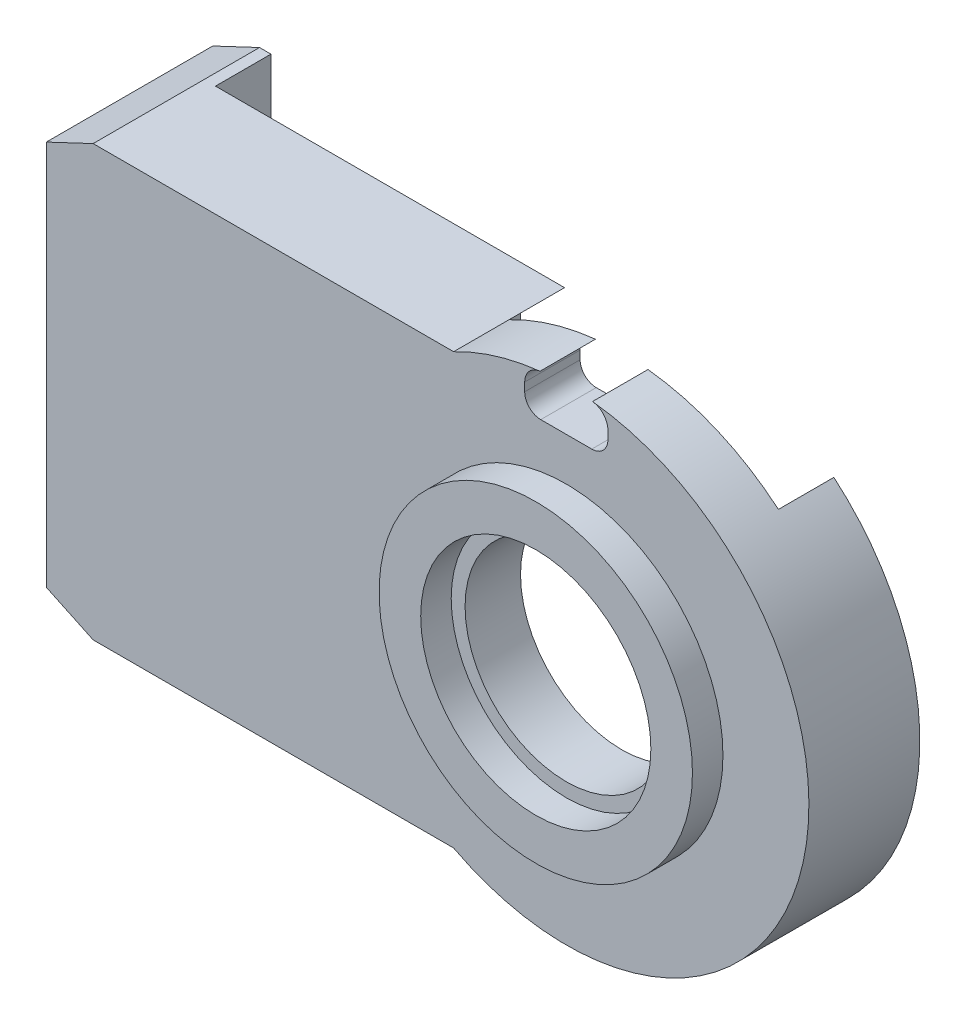
SolidWorks part; units mm, degrees
ref_plane "Спереди" through (0, 0, 0) normal (0, 0, 1) x (1, 0, 0)
ref_plane "Сверху" through (0, 0, 0) normal (0, 1, 0) x (1, 0, 0)
ref_plane "Справа" through (0, 0, 0) normal (1, 0, 0) x (0, 0, -1)
sketch "Эскиз основы" plane through (0, 0, 0) normal (0, 0, 1) x (1, 0, 0)
  line L0 (5.65, 6.6813) -> (5.65, -6.6813)
  line L1 (-5.65, 6.6813) -> (-5.65, -6.6813)
  line L2 (-17.062, 7.75) -> (-18.75, 6.9532)
  line L3 (-17.062, 7.75) -> (-4.062, 7.75)
  line L4 (-17.062, -7.75) -> (-4.062, -7.75)
  line L5 (-4.062, 7.75) -> (-4.062, -7.75)
  line L6 (-17.062, -7.75) -> (-18.75, -6.9532)
  line L11 (-18.75, 6.9532) -> (-18.75, -6.9532)
  line L12 (-16.65, 7.75) -> (-16.65, -7.75)
  arc A0 (-5.65, -6.6813) -> (5.65, -6.6813) centre (0, 0) ccw
  arc A1 (-5.65, -6.6813) -> (5.65, -6.6813) centre (0, 0) ccw
  arc A2 (5.65, 6.6813) -> (-5.65, 6.6813) centre (0, 0) ccw
  circle A3 centre (0, 0) radius 8.75
  circle A10 centre (0, 0) radius 3.65
  point P6 (0, 0)
  point P7 (-4.062, 0)
  point P8 (-18.75, 0)
  point P9 (0, 0)
  point P10 (5.65, 0)
  point P15 (0, 8.75)
  dimension "D1" = 8.75
  dimension "D3" = 17.5
  dimension "D8" = 18.75
  dimension "D11" = 7.3
  dimension "D2" = 11.3
  dimension "D4" = 15.5
  dimension "D5" = 13
  dimension "D6" = 6.9532
  dimension "D9" = 11
extrude "Заготовка" add sketch "Эскиз основы" along normal blind 4 contours L6 L4 A0 A3 A2 L3 L2 | L1 A3 | L5 A2 L1 A0 | L0 A2 L5 A0 | L0 A3 | L2 L11 L6 L4 L5 L3 region at (6.911, 0, 0) region at (5.4499, 0, 0) region at (-11.9356, 0, 0) region at (-4.8366, 0, 0) region at (-6.911, 0, 0)
extrude "Вырез под резистор" cut sketch "Эскиз1<3>" along normal blind 2 contours L0 A2 L5 A0 | L5 A2 L1 A0 region at (5.4499, 0, 0) region at (-4.8366, 0, 0)
sketch "Эскиз1<3>" plane through (0, 0, 0) normal (0, 0, 1) x (1, 0, 0) same geometry as "Эскиз основы"
sketch "Эскиз выемки" plane through (0, 0, 2) normal (0, 0, -1) x (-1, 0, 0)
  line L3 (-3.65, 0) -> (3.65, 0) construction
  line L4 (-1.5, 7.78) -> (-1.5, 8.0822)
  line L5 (1.5, 7.78) -> (1.5, 8.0822)
  line L6 (0.92, 7.2) -> (-0.92, 7.2)
  circle A5 centre (0, 0) radius 3.65 construction
  arc A6 (-0.9471, 8.6986) -> (-1.5, 8.0822) centre (-0.88, 8.0822) ccw
  arc A7 (0.9471, 8.6986) -> (1.5, 8.0822) centre (0.88, 8.0822) cw
  arc A8 (-1.5, 7.78) -> (-0.92, 7.2) centre (-0.92, 7.78) ccw
  arc A9 (1.5, 7.78) -> (0.92, 7.2) centre (0.92, 7.78) cw
  arc A10 (0.9471, 8.6986) -> (-0.9471, 8.6986) centre (0, 0) ccw
  arc A11 (4.062, 7.75) -> (-5.65, 6.6813) centre (0, 0) ccw construction
  point P0 (0, 0)
  point P4 (0, 7.2)
  dimension "D1" = 7.2
  dimension "D5" = 0.62
  dimension "D4" = 0.58
  dimension "D6" = 3
extrude "Вырез под выемку резистора" cut sketch "Эскиз выемки" against normal blind 2
extrude "Зажим проводов" add sketch "Эскиз1<5>" against normal blind 2 contours L6 L2 region at (-17.679, 0, 0)
sketch "Эскиз1<5>" plane through (0, 0, 0) normal (0, 0, 1) x (1, 0, 0) same geometry as "Эскиз основы"
sketch "Эскиз4" plane through (0, 0, 4) normal (0, 0, 1) x (1, 0, 0)
  circle A0 centre (0, 0) radius 4.15
  circle A1 centre (0, 0) radius 5.65
  dimension "D1" = 8.3
  dimension "D2" = 1.5
extrude "Бобышка-Вытянуть4" add sketch "Эскиз4" along normal blind 1.1 contours A1 A0 region at (-5.4902, 0, 4)
